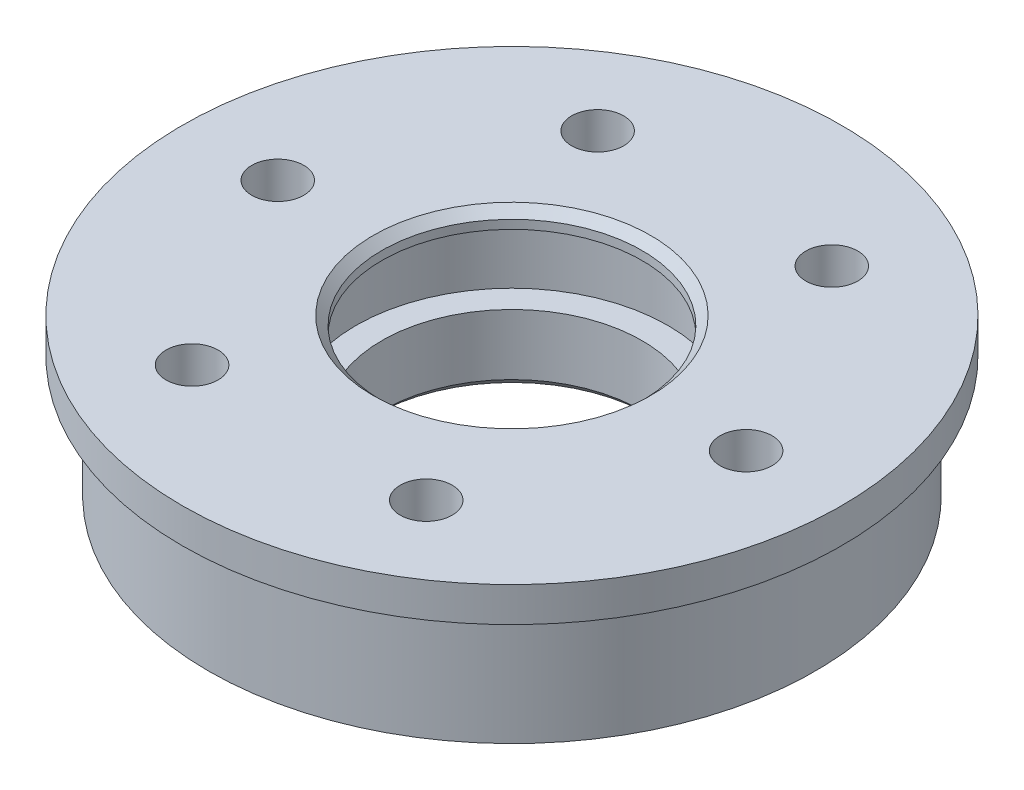
SolidWorks part; units mm, degrees
ref_plane "Front Plane" through (0, 0, 0) normal (0, 0, 1) x (1, 0, 0)
ref_plane "Top Plane" through (0, 0, 0) normal (0, 1, 0) x (1, 0, 0)
ref_plane "Right Plane" through (0, 0, 0) normal (1, 0, 0) x (0, 0, -1)
sketch "Sketch1" plane through (0, 0, 0) normal (0, 1, 0) x (1, 0, 0)
  circle A0 centre (0, 0) radius 13.5 construction
  circle A1 centre (13.5, 0) radius 1.5
  circle A2 centre (6.75, -11.6913) radius 1.5
  circle A3 centre (-6.75, -11.6913) radius 1.5
  circle A4 centre (-13.5, 0) radius 1.5
  circle A5 centre (-6.75, 11.6913) radius 1.5
  circle A6 centre (6.75, 11.6913) radius 1.5
  circle A7 centre (0, 0) radius 17.5
  circle A8 centre (0, 0) radius 7.5
  point P17 (0, 0)
  dimension "D1" = 27
  dimension "D2" = 3
  dimension "D4" = 35
  dimension "D5" = 15
  dimension "D3" = 6
extrude "Boss-Extrude1" add sketch "Sketch1" along normal mid plane 9
sketch "Sketch2" plane through (0, 0, 0) normal (0, 1, 0) x (1, 0, 0)
  circle A0 centre (0, 0) radius 9
  dimension "D1" = 18
extrude "Cut-Extrude1" cut sketch "Sketch2" along normal blind 4 from offset 0.5 offset against normal yes
sketch "Sketch3" plane through (0, -4.5, 0) normal (0, -1, 0) x (1, 0, 0)
  circle A0 centre (0, 0) radius 12
  circle A1 centre (0, 0) radius 15
  circle A2 centre (-13.5, 0) radius 1.5 construction
extrude "Boss-Extrude2" add sketch "Sketch3" against normal blind 1.5
chamfer "Chamfer1" distance 0.5 angle 45 2 edges at (0, -4.5, 7.5) (0, 4.5, 7.5)
sketch "Sketch4" plane through (0, 4.5, 0) normal (0, 1, 0) x (1, 0, 0)
  circle A0 centre (0, 0) radius 19
  circle A1 centre (0, 0) radius 17.5 construction
  circle A2 centre (0, 0) radius 17.5
  dimension "D1" = 1.5
extrude "Boss-Extrude3" add sketch "Sketch4" against normal blind 2
equation "\"D5@Sketch1\"=18-3"
